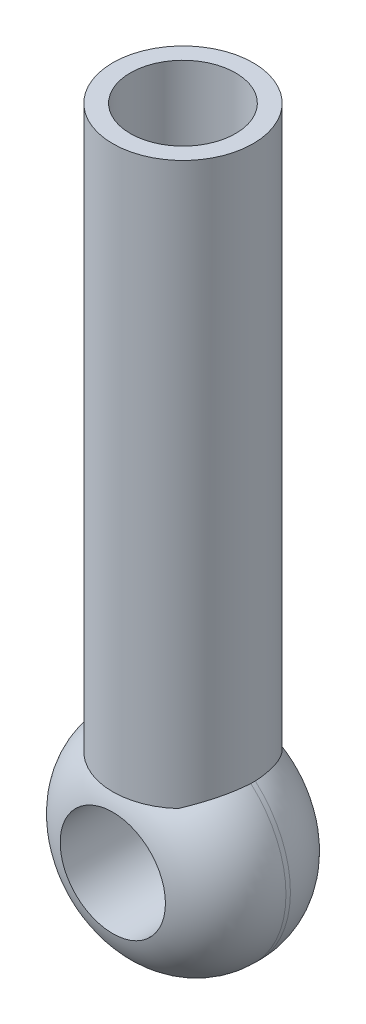
SolidWorks part; units mm, degrees
ref_plane "Front Plane" through (0, 0, 0) normal (0, 0, 1) x (1, 0, 0)
ref_plane "Top Plane" through (0, 0, 0) normal (0, 1, 0) x (1, 0, 0)
ref_plane "Right Plane" through (0, 0, 0) normal (1, 0, 0) x (0, 0, -1)
sketch "Sketch1" plane through (0, 0, 0) normal (0, 0, 1) x (1, 0, 0)
  circle A0 centre (0, 0) radius 7.5
  circle A1 centre (0, 0) radius 15
  dimension "D1" = 15
  dimension "D2" = 30
extrude "Boss-Extrude1" add sketch "Sketch1" along normal blind 20
fillet "Fillet1" radius 10 2 edges at (15, 0, 0) (15, 0, 20)
sketch "Sketch2" plane through (0, 0, 0) normal (0, 1, 0) x (1, 0, 0)
  circle A0 centre (0, -10) radius 10
  dimension "D2" = 20
  dimension "D1" = 10
extrude "Boss-Extrude3" add sketch "Sketch2" along normal blind 80 from offset 10
sketch "Sketch5" plane through (0, 90, 0) normal (0, 1, 0) x (1, 0, 0)
  circle A0 centre (0, -10) radius 7.5
  dimension "D1" = 15
extrude "Cut-Extrude3" cut sketch "Sketch5" against normal blind 30
